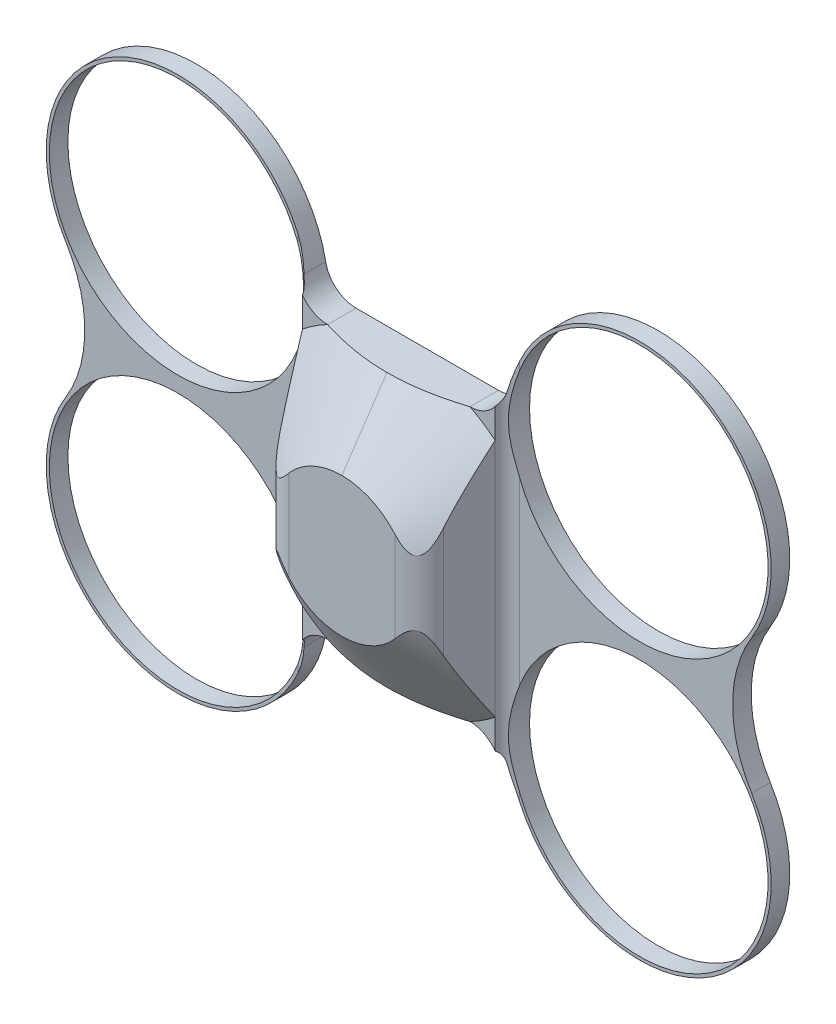
SolidWorks part; units mm, degrees
ref_plane "Front Plane" through (0, 0, 0) normal (0, 0, 1) x (1, 0, 0)
ref_plane "Top Plane" through (0, 0, 0) normal (0, 1, 0) x (1, 0, 0)
ref_plane "Right Plane" through (0, 0, 0) normal (1, 0, 0) x (0, 0, -1)
sketch "Sketch1" plane through (0, 0, 0) normal (0, 0, 1) x (1, 0, 0)
  line L0 (0, 0) -> (0, 31.402) construction
  line L1 (0, 0) -> (-57.7561, 0) construction
  line L2 (22.9612, 44) -> (-22.9612, 44)
  line L3 (22.9612, -44) -> (-22.9612, -44)
  arc A0 (110.703, 21.7381) -> (32.7781, 52.0952) centre (74.5, 44) ccw
  arc A1 (-110.703, 21.7381) -> (-32.7781, 52.0952) centre (-74.5, 44) cw
  arc A2 (110.703, -21.7381) -> (32.7781, -52.0952) centre (74.5, -44) cw
  arc A3 (-110.703, -21.7381) -> (-32.7781, -52.0952) centre (-74.5, -44) ccw
  arc A4 (110.703, 21.7381) -> (110.703, -21.7381) centre (146.0542, 0) ccw
  arc A5 (22.9612, 44) -> (32.7781, 52.0952) centre (22.9612, 54) ccw
  arc A6 (-22.9612, 44) -> (-32.7781, 52.0952) centre (-22.9612, 54) cw
  arc A7 (-110.703, 21.7381) -> (-110.703, -21.7381) centre (-146.0542, 0) cw
  arc A8 (22.9612, -44) -> (32.7781, -52.0952) centre (22.9612, -54) cw
  arc A9 (-22.9612, -44) -> (-32.7781, -52.0952) centre (-22.9612, -54) ccw
  point P23 (0, 44)
  dimension "D1" = 85
  dimension "D2" = 173
  dimension "D3" = 234
  dimension "D4" = 83
  dimension "D5" = 44
  dimension "D6" = 20
extrude "Boss-Extrude1" add sketch "Sketch1" along normal blind 27.56
sketch "Sketch2" plane through (0, 0, 0) normal (0, 1, 0) x (1, 0, 0)
  line L0 (117, -6) -> (35.7676, -6)
  line L1 (117, -27.56) -> (117, 0) construction
  line L2 (31.1085, -9.1854) -> (26.4332, -21.1893)
  line L3 (22.9612, -27.56) -> (32.7781, -27.56) construction
  line L9 (0, -1013.78) -> (0, 48986.22) construction
  line L10 (17.115, -27.56) -> (117, -27.56)
  line L11 (117, -27.56) -> (117, -6)
  line L12 (117, 0) -> (32.7781, 0) construction
  line L13 (-117, -27.56) -> (-117, -6)
  line L14 (-17.115, -27.56) -> (-117, -27.56)
  line L15 (-31.1085, -9.1854) -> (-26.4332, -21.1893)
  line L16 (-117, -6) -> (-35.7676, -6)
  arc A0 (26.4332, -21.1893) -> (17.115, -27.56) centre (17.115, -17.56) cw
  arc A1 (35.7676, -6) -> (31.1085, -9.1854) centre (35.7676, -11) ccw
  arc A2 (-35.7676, -6) -> (-31.1085, -9.1854) centre (-35.7676, -11) cw
  arc A3 (-26.4332, -21.1893) -> (-17.115, -27.56) centre (-17.115, -17.56) ccw
  point P20 (23.9519, -27.56)
  point P29 (-23.9519, -27.56)
  dimension "D3" = 10
  dimension "D4" = 5
  dimension "D1" = 17.115
  dimension "D2" = 111.28
  dimension "D5" = 6
extrude "Cut-Extrude1" cut sketch "Sketch2" against normal through all both and the other way through all
sketch "Sketch3" plane through (0, 0, 0) normal (0, 0, -1) x (-1, 0, 0)
  line L0 (-1000, 0) -> (49000, 0) construction
  line L1 (0, 44.759) -> (0, 50044.759) construction
  circle A0 centre (74.5, 44) radius 41.5
  arc A1 (110.703, 21.7381) -> (32.7781, 52.0952) centre (74.5, 44) ccw construction
  circle A2 centre (-74.5, 44) radius 41.5
  circle A3 centre (-74.5, 44) radius 41.5
  circle A4 centre (74.5, 44) radius 41.5
  circle A5 centre (74.5, -44) radius 41.5
  circle A6 centre (-74.5, -44) radius 41.5
  dimension "D1" = 1
extrude "Cut-Extrude2" cut sketch "Sketch3" against normal through all both contours A2 | A6 | A0 | A5 region at (-74.5, 44, 0) region at (74.5, 44, 0) region at (-74.5, -44, 0) region at (74.5, -44, 0)
sketch "Sketch4" plane through (0, 0, 27.56) normal (0, 0, 1) x (1, 0, 0)
  circle A0 centre (0, 0) radius 22.5
  dimension "D1" = 45
sketch "Sketch5" plane through (0, 0, 0) normal (1, 0, 0) x (0, 0, -1)
  line L0 (-27.56, 22.5) -> (-9.1854, 49.6392)
  line L1 (-27.56, 44) -> (-27.56, -44) construction
  line L3 (-27.56, 48.2016) -> (-27.56, 22.5)
  line L4 (-27.56, 22.5) -> (-27.56, -22.5) construction
  line L5 (-9.1854, 49.6392) -> (-9.1854, 86.5)
  line L6 (-9.1854, 86.5) -> (-27.56, 86.5)
  line L7 (-27.56, 86.5) -> (-27.56, 48.2016)
  line L8 (0, 86.5) -> (-6, 86.5) construction
  dimension "D1" = 34.1
sweep "Cut-Sweep1" cut profiles "Sketch5" path "Sketch4"
sketch "Sketch8" plane through (0, 0, 0) normal (1, 0, 0) x (0, 0, -1)
  line L0 (-4.7766, 43.9741) -> (-4.7766, 48.4165)
  line L1 (-4.7766, 48.4165) -> (-8.2513, 48.4165)
  line L2 (-8.2513, 48.4165) -> (-8.2513, 47.5075)
  line L3 (-8.2513, 47.5075) -> (-6.5139, 47.5075)
  line L4 (-6.5139, 47.5075) -> (-6.5139, 43.9741)
  line L5 (-6.5139, 43.9741) -> (-4.7766, 43.9741)
